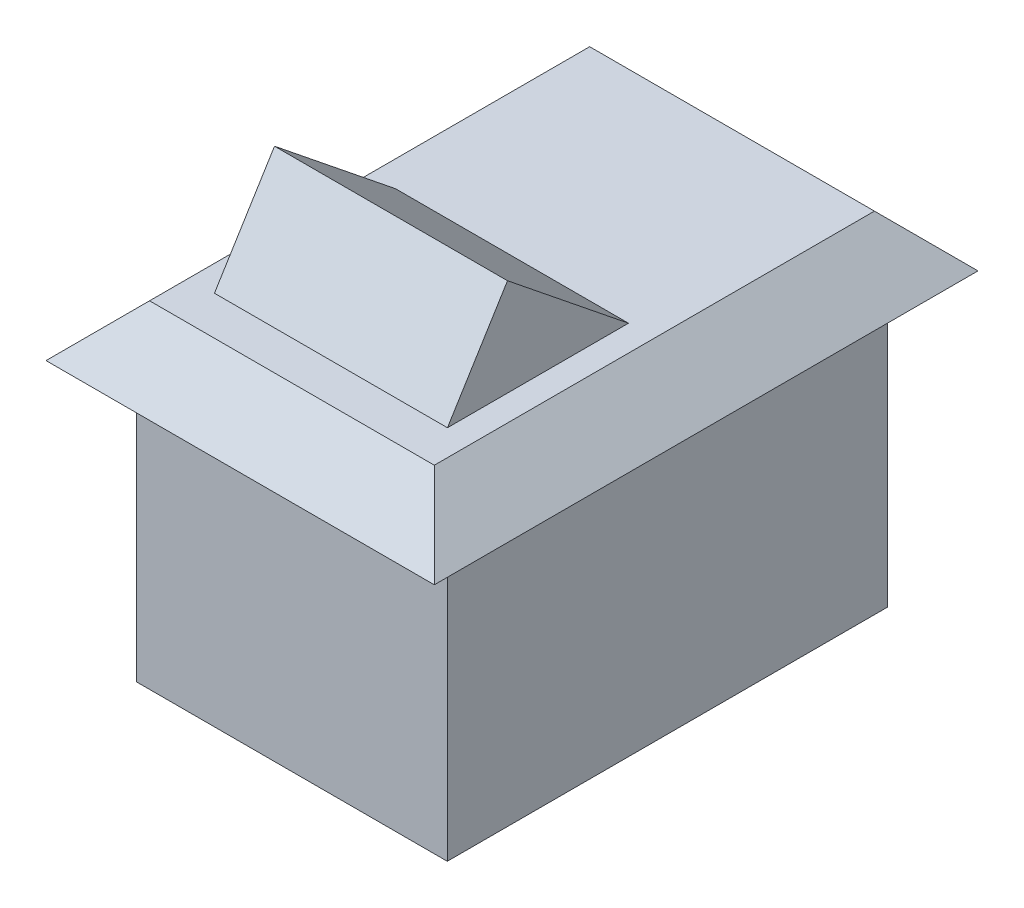
SolidWorks part; units mm, degrees
ref_plane "前视基准面" through (0, 0, 0) normal (0, 0, 1) x (1, 0, 0)
ref_plane "上视基准面" through (0, 0, 0) normal (0, 1, 0) x (1, 0, 0)
ref_plane "右视基准面" through (0, 0, 0) normal (1, 0, 0) x (0, 0, -1)
sketch "草图1" plane through (0, 0, 0) normal (0, 1, 0) x (1, 0, 0)
  line L1 (-6, -8.5) -> (6, -8.5)
  line L2 (-6, -8.5) -> (-6, 8.5)
  line L3 (-6, 8.5) -> (6, 8.5)
  line L4 (6, -8.5) -> (6, 8.5)
  line L5 (-6, -8.5) -> (6, 8.5) construction
  line L6 (-6, 8.5) -> (6, -8.5) construction
  point P0 (0, 0)
  dimension "D1" = 12
  dimension "D2" = 17
extrude "凸台-拉伸1" add sketch "草图1" along normal blind 11
sketch "草图2" plane through (0, 11, 0) normal (0, 1, 0) x (1, 0, 0)
  line L1 (-7.5, -10.5) -> (7.5, -10.5)
  line L2 (-7.5, -10.5) -> (-7.5, 10.5)
  line L3 (-7.5, 10.5) -> (7.5, 10.5)
  line L4 (7.5, -10.5) -> (7.5, 10.5)
  line L5 (-7.5, -10.5) -> (7.5, 10.5) construction
  line L6 (-7.5, 10.5) -> (7.5, -10.5) construction
  point P0 (0, 0)
  dimension "D1" = 15
  dimension "D2" = 21
extrude "凸台-拉伸2" add sketch "草图2" along normal blind 2
chamfer "倒角1" distance 2 angle 45 4 edges at (0, 13, -10.5) (7.5, 13, 0) (0, 13, 10.5) (-7.5, 13, 0)
sketch "草图3" plane through (0, 0, 0) normal (1, 0, 0) x (0, 0, -1)
  line L0 (-6.9936, 13) -> (-4.6739, 16.7583)
  line L1 (-8.5, 13) -> (8.5, 13) construction
  line L2 (-4.6739, 16.7583) -> (0, 13)
  line L3 (0, 13) -> (-6.9936, 13)
extrude "凸台-拉伸3" add sketch "草图3" along normal mid plane 9
